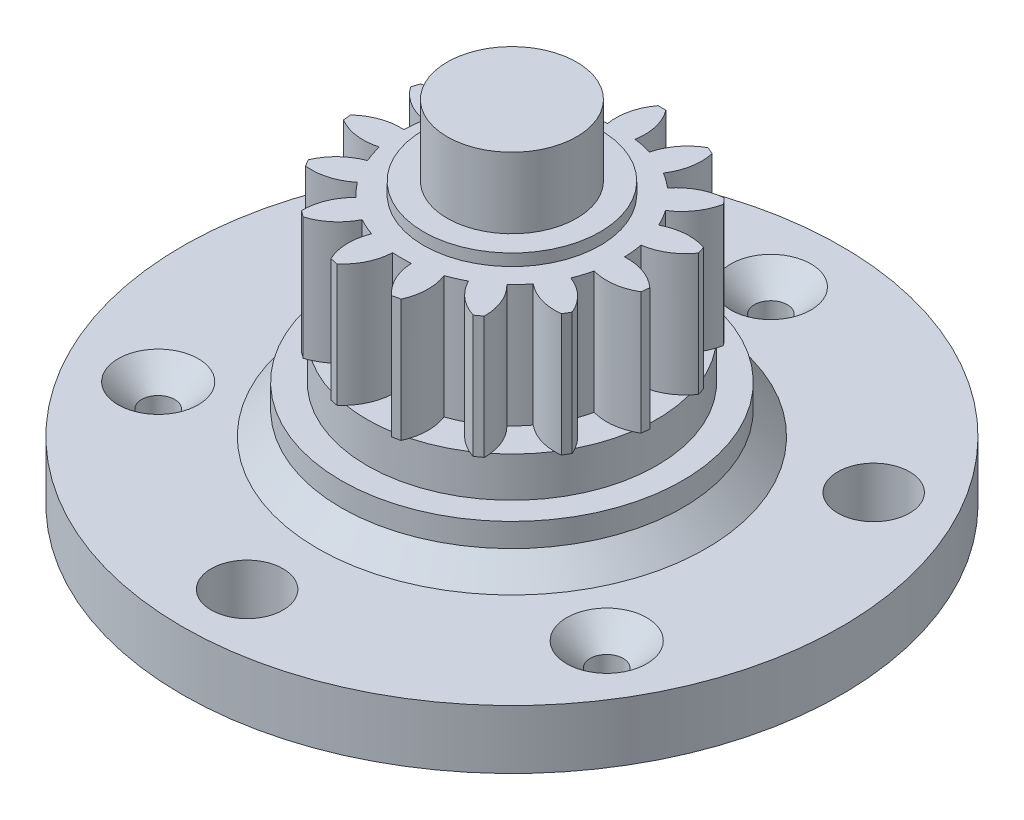
SolidWorks part; units mm, degrees
other "Marcação1"
sketch "Esboço14" plane through (-28, 0, 28) normal (-0.279, -0.8774, 0.3904) x (0.9389, -0.3346, -0.0809)
ref_plane "Plano frontal" through (0, 0, 0) normal (0, 0, 1) x (1, 0, 0)
ref_plane "Plano superior" through (0, 0, 0) normal (0, 1, 0) x (1, 0, 0)
ref_plane "Plano direito" through (0, 0, 0) normal (1, 0, 0) x (0, 0, -1)
sketch "Esboço1" plane through (0, 0, 0) normal (0, 1, 0) x (1, 0, 0)
  circle A0 centre (0, 0) radius 28
  dimension "D1" = 56
extrude "Ressalto-extrusão1" add sketch "Esboço1" along normal blind 5
sketch "Esboço5" plane through (0, 0, 0) normal (1, 0, 0) x (0, 0, -1)
  line L0 (0, 5) -> (-16.5, 5)
  line L1 (28, 5) -> (-28, 5) construction
  line L2 (-16.5, 5) -> (-14.5, 7)
  line L3 (-14.5, 7) -> (-14.5, 9)
  line L4 (-14.5, 9) -> (-12.3, 9)
  line L5 (-12.3, 9) -> (-12.3, 12.4)
  line L7 (0, 29.8) -> (0, 5)
  line L8 (-12.3, 12.4) -> (-9.37, 12.4)
  line L9 (-9.37, 12.4) -> (-9.37, 22.8)
  line L10 (-9.37, 22.8) -> (-7.5, 22.8)
  line L11 (-7.5, 22.8) -> (-7.5, 23.8)
  line L12 (-7.5, 23.8) -> (-5.5, 23.8)
  line L13 (-5.5, 23.8) -> (-5.5, 29.8)
  line L14 (-5.5, 29.8) -> (0, 29.8)
  point P4 (0, 12.4)
  point P17 (0, 0)
  point P18 (0, 18.7951)
  dimension "D1" = 16.5
  dimension "D2" = 14.5
  dimension "D3" = 2
  dimension "D4" = 2
  dimension "D5" = 12.3
  dimension "D6" = 3.4
  dimension "D7" = 10.4
  dimension "D8" = 9.37
  dimension "D9" = 7.5
  dimension "D10" = 1
  dimension "D11" = 6
  dimension "D12" = 5.5
revolve "Revolução1" add sketch "Esboço5" angle 360 about L7
sketch "Esboço6" plane through (0, 0, 0) normal (0, -1, 0) x (1, 0, 0)
  circle A0 centre (0, 0) radius 10.75
  dimension "D1" = 21.5
extrude "Corte-extrusão1" cut sketch "Esboço6" against normal blind 5
sketch "Esboço7" plane through (0, 5, 0) normal (0, -1, 0) x (1, 0, 0)
  circle A0 centre (0, 0) radius 9
  dimension "D1" = 18
extrude "Corte-extrusão2" cut sketch "Esboço7" against normal blind 0.4
sketch "Esboço8" plane through (0, 0, 0) normal (0, -1, 0) x (1, 0, 0)
  line L0 (0, 0) -> (0, 22.5) construction
  circle A0 centre (0, 22.5) radius 3.05
  dimension "D2" = 6.1
  dimension "D1" = 22.5
extrude "Corte-extrusão3" cut sketch "Esboço8" against normal up to next
pattern_circular "PadrãoCircular1" count 3 over 360 about axis through (0, 0, 0) along (0, 1, 0) of "Corte-extrusão3"
sketch "Esboço9" plane through (0, 0, 0) normal (0, -1, 0) x (1, 0, 0)
  line L0 (0, 0) -> (0, 22.5) construction
  line L1 (0, 0) -> (-19.0526, 11) construction
  circle A0 centre (-19.0526, 11) radius 1.4
  dimension "D3" = 2.8
  dimension "D1" = 60
  dimension "D2" = 22
extrude "Corte-extrusão4" cut sketch "Esboço9" against normal up to next
pattern_circular "PadrãoCircular2" count 3 over 360 about axis through (0, 0, 0) along (0, 1, 0) of "Corte-extrusão4"
sketch "Esboço10" plane through (0, 0, 0) normal (0, -1, 0) x (1, 0, 0)
  line L0 (0, 0) -> (0, 22.5) construction
  line L1 (0, 0) -> (-17.6777, 17.6777) construction
  circle A0 centre (-17.6777, 17.6777) radius 1.25
  dimension "D3" = 2.5
  dimension "D1" = 45
  dimension "D2" = 25
ref_plane "Plano1" through (0, 3, 0) normal (0, -1, 0) x (-1, 0, 0)
sketch "Esboço12" plane through (0, 3, 0) normal (0, -1, 0) x (-1, 0, 0)
  circle A0 centre (17.6777, -17.6777) radius 0.75
  dimension "D1" = 1.5
loft "Loft de corte1" cut profiles "Esboço12", "Esboço10" connector at (-18.2603, 3, 17.2054) connector at (-18.9149, 0, 17.4992)
pattern_circular "PadrãoCircular3" count 3 over 360 about axis through (0, 0, 0) along (0, 1, 0) of "Loft de corte1"
chamfer "Chanfro1" distance 2 angle 45 1 edges at (-19.0526, 5, 12.4)
chamfer "Chanfro2" distance 2 angle 45 2 edges at (19.0526, 5, 12.4) (0, 5, -20.6)
sketch "Esboço15" plane through (0, 22.8, 0) normal (0, 1, 0) x (1, 0, 0)
  line L0 (0, 0) -> (0, 12.75) construction
  line L1 (0.335, 12.75) -> (-0.335, 12.75)
  line L2 (0, 0) -> (3.269, 10.0539) construction
  arc A0 (1.1678, 9.2969) -> (-1.1678, 9.2969) centre (0, 0) ccw
  circle A1 centre (0, 0) radius 9.37 construction
  arc A2 (-0.335, 12.75) -> (-1.1678, 9.2969) centre (3.269, 10.0539) ccw
  arc A3 (0.335, 12.75) -> (1.1678, 9.2969) centre (-3.269, 10.0539) cw
  point P4 (0, 12.75)
  dimension "D1" = 12.75
  dimension "D2" = 0.67
  dimension "D3" = 18.012
  dimension "D4" = 10.572
extrude "Ressalto-extrusão2" add sketch "Esboço15" against normal up to surface (10.4 mm away) up to face at (0, 12.4, 12.3)
pattern_circular "PadrãoCircular4" count 15 over 360 about axis through (0, 29.8, 0) along (0, 1, 0) of "Ressalto-extrusão2" reverse direction yes
